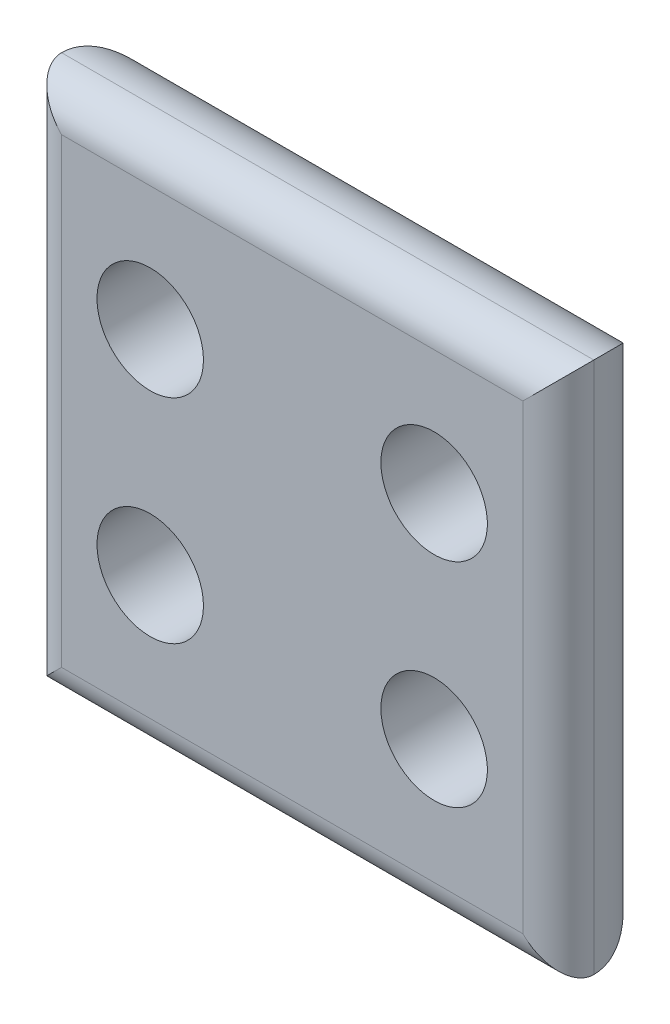
SolidWorks part; units mm, degrees
ref_plane "Front Plane" through (0, 0, 0) normal (0, 0, 1) x (1, 0, 0)
ref_plane "Top Plane" through (0, 0, 0) normal (0, 1, 0) x (1, 0, 0)
ref_plane "Right Plane" through (0, 0, 0) normal (1, 0, 0) x (0, 0, -1)
sketch "Sketch1" plane through (0, 0, 0) normal (0, 0, 1) x (1, 0, 0)
  line L1 (-7.5, 7.5) -> (7.5, 7.5)
  line L2 (-7.5, 7.5) -> (-7.5, -7.5)
  line L3 (-7.5, -7.5) -> (7.5, -7.5)
  line L4 (7.5, 7.5) -> (7.5, -7.5)
  line L5 (-7.5, 7.5) -> (7.5, -7.5) construction
  line L6 (-7.5, -7.5) -> (7.5, 7.5) construction
  circle A0 centre (-4, 3) radius 1.5
  circle A1 centre (-4, -3) radius 1.5
  circle A2 centre (4, -3) radius 1.5
  circle A3 centre (4, 3) radius 1.5
  point P0 (0, 0)
  dimension "D5" = 3
  dimension "D1" = 6
  dimension "D2" = 15
  dimension "D3" = 15
  dimension "D4" = 4
extrude "Boss-Extrude1" add sketch "Sketch1" along normal blind 3
fillet "Fillet3" radius 1 4 edges at (7.5, 0, 3) (0, -7.5, 3) (-7.5, 0, 3) (0, 7.5, 3)
fillet "Fillet4" radius 2 4 edges at (0, -7.5, 0) (-7.5, 0, 0) (7.5, 0, 0) (0, 7.5, 0)
